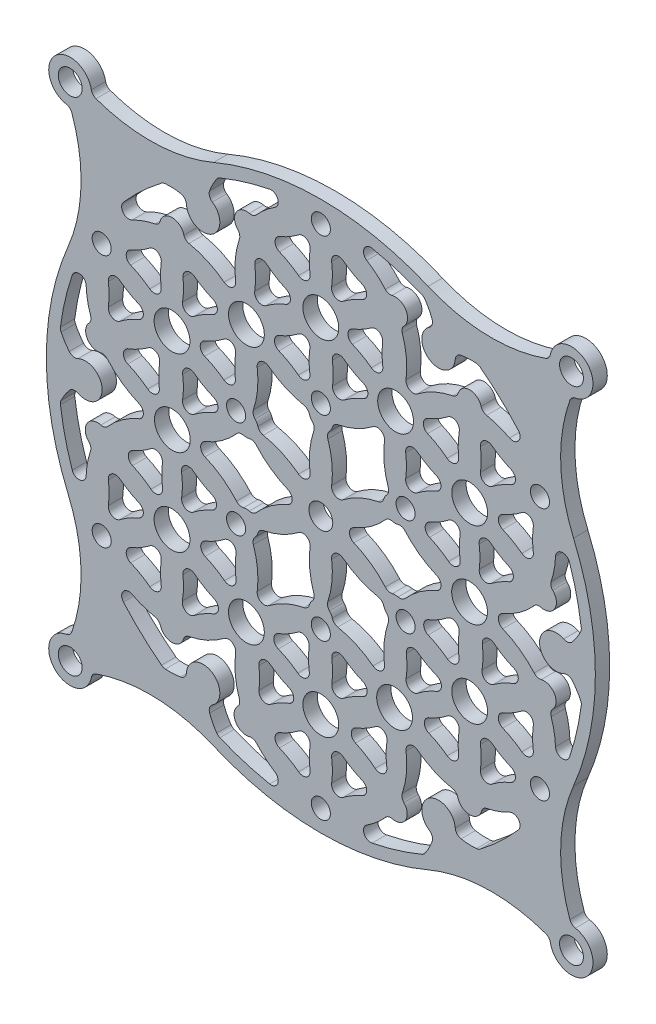
SolidWorks part; units mm, degrees
material "PC Alta Viscosidade"
ref_plane "Plano frontal" through (0, 0, 0) normal (0, 0, 1) x (1, 0, 0)
ref_plane "Plano superior" through (0, 0, 0) normal (0, 1, 0) x (1, 0, 0)
ref_plane "Plano direito" through (0, 0, 0) normal (1, 0, 0) x (0, 0, -1)
sketch "Esboço1" plane through (0, 0, 0) normal (0, 0, 1) x (1, 0, 0)
  line L1 (-60, 60) -> (60, 60)
  line L2 (-60, 60) -> (-60, -60)
  line L3 (-60, -60) -> (60, -60)
  line L4 (60, 60) -> (60, -60)
  line L5 (-60, 60) -> (60, -60) construction
  line L6 (-60, -60) -> (60, 60) construction
  point P0 (0, 0)
  dimension "D1" = 120
  dimension "D2" = 120
extrude "Ressalto-extrusão1" add sketch "Esboço1" along normal blind 3
sketch "Esboço2" plane through (0, 0, 3) normal (0, 0, 1) x (1, 0, 0)
  circle A0 centre (-52.5, 52.5) radius 2.5
  circle A1 centre (52.5, 52.5) radius 2.5
  circle A2 centre (52.5, -52.5) radius 2.5
  circle A3 centre (-52.5, -52.5) radius 2.5
  dimension "D5" = 5
  dimension "D1" = 105
  dimension "D2" = 105
  dimension "D3" = 52.5
  dimension "D4" = 52.5
extrude "Corte-extrusão1" cut sketch "Esboço2" against normal through all
sketch "Esboço3" plane through (0, 0, 3) normal (0, 0, 1) x (1, 0, 0)
  line L0 (0, 54) -> (0, 36) construction
  line L1 (0, 36) -> (0, 18) construction
  line L2 (0, 18) -> (0, 0) construction
  line L3 (0, 36) -> (-15.5885, 45) construction
  line L4 (-15.5885, 45) -> (-15.5885, 27) construction
  line L5 (-15.5885, 27) -> (0, 36) construction
  line L6 (0, 36) -> (15.5885, 45) construction
  line L7 (15.5885, 45) -> (15.5885, 27) construction
  line L8 (15.5885, 27) -> (0, 36) construction
  line L9 (0, 54) -> (-15.5885, 45) construction
  line L10 (0, 54) -> (15.5885, 45) construction
  line L11 (-15.5885, 27) -> (0, 18) construction
  line L12 (0, 18) -> (15.5885, 27) construction
  line L13 (46.7654, 27) -> (31.1769, 18) construction
  line L14 (31.1769, 18) -> (15.5885, 9) construction
  line L15 (15.5885, 9) -> (0, 0) construction
  line L16 (31.1769, 18) -> (31.1769, 36) construction
  line L17 (31.1769, 36) -> (15.5885, 27) construction
  line L18 (15.5885, 27) -> (31.1769, 18) construction
  line L19 (31.1769, 18) -> (46.7654, 9) construction
  line L20 (46.7654, 9) -> (31.1769, 0) construction
  line L21 (31.1769, 0) -> (31.1769, 18) construction
  line L22 (46.7654, 27) -> (31.1769, 36) construction
  line L23 (46.7654, 27) -> (46.7654, 9) construction
  line L24 (15.5885, 27) -> (15.5885, 9) construction
  line L25 (15.5885, 9) -> (31.1769, 0) construction
  line L26 (46.7654, -27) -> (31.1769, -18) construction
  line L27 (31.1769, -18) -> (15.5885, -9) construction
  line L28 (15.5885, -9) -> (0, 0) construction
  line L29 (31.1769, -18) -> (46.7654, -9) construction
  line L30 (46.7654, -9) -> (31.1769, 0) construction
  line L31 (31.1769, 0) -> (31.1769, -18) construction
  line L32 (31.1769, -18) -> (31.1769, -36) construction
  line L33 (31.1769, -36) -> (15.5885, -27) construction
  line L34 (15.5885, -27) -> (31.1769, -18) construction
  line L35 (46.7654, -27) -> (46.7654, -9) construction
  line L36 (46.7654, -27) -> (31.1769, -36) construction
  line L37 (31.1769, 0) -> (15.5885, -9) construction
  line L38 (15.5885, -9) -> (15.5885, -27) construction
  line L39 (0, -54) -> (0, -36) construction
  line L40 (0, -36) -> (0, -18) construction
  line L41 (0, -18) -> (0, 0) construction
  line L42 (0, -36) -> (15.5885, -45) construction
  line L43 (15.5885, -45) -> (15.5885, -27) construction
  line L44 (15.5885, -27) -> (0, -36) construction
  line L45 (0, -36) -> (-15.5885, -45) construction
  line L46 (-15.5885, -45) -> (-15.5885, -27) construction
  line L47 (-15.5885, -27) -> (0, -36) construction
  line L48 (0, -54) -> (15.5885, -45) construction
  line L49 (0, -54) -> (-15.5885, -45) construction
  line L50 (15.5885, -27) -> (0, -18) construction
  line L51 (0, -18) -> (-15.5885, -27) construction
  line L52 (-46.7654, -27) -> (-31.1769, -18) construction
  line L53 (-31.1769, -18) -> (-15.5885, -9) construction
  line L54 (-15.5885, -9) -> (0, 0) construction
  line L55 (-31.1769, -18) -> (-31.1769, -36) construction
  line L56 (-31.1769, -36) -> (-15.5885, -27) construction
  line L57 (-15.5885, -27) -> (-31.1769, -18) construction
  line L58 (-31.1769, -18) -> (-46.7654, -9) construction
  line L59 (-46.7654, -9) -> (-31.1769, 0) construction
  line L60 (-31.1769, 0) -> (-31.1769, -18) construction
  line L61 (-46.7654, -27) -> (-31.1769, -36) construction
  line L62 (-46.7654, -27) -> (-46.7654, -9) construction
  line L63 (-15.5885, -27) -> (-15.5885, -9) construction
  line L64 (-15.5885, -9) -> (-31.1769, 0) construction
  line L65 (-46.7654, 27) -> (-31.1769, 18) construction
  line L66 (-31.1769, 18) -> (-15.5885, 9) construction
  line L67 (-15.5885, 9) -> (0, 0) construction
  line L68 (-31.1769, 18) -> (-46.7654, 9) construction
  line L69 (-46.7654, 9) -> (-31.1769, 0) construction
  line L70 (-31.1769, 0) -> (-31.1769, 18) construction
  line L71 (-31.1769, 18) -> (-31.1769, 36) construction
  line L72 (-31.1769, 36) -> (-15.5885, 27) construction
  line L73 (-15.5885, 27) -> (-31.1769, 18) construction
  line L74 (-46.7654, 27) -> (-46.7654, 9) construction
  line L75 (-46.7654, 27) -> (-31.1769, 36) construction
  line L76 (-31.1769, 0) -> (-15.5885, 9) construction
  line L77 (-15.5885, 9) -> (-15.5885, 27) construction
  line L78 (-46.7654, 27) -> (-49.4666, 28.5596) construction
  line L79 (-46.7654, -27) -> (-49.4666, -28.5596) construction
  line L80 (0, -54) -> (0, -57.1191) construction
  line L81 (46.7654, -27) -> (49.4666, -28.5596) construction
  line L82 (46.7668, 27.0008) -> (49.468, 28.5603) construction
  line L83 (0, 54.0016) -> (0, 57.1207) construction
  line L84 (0, 0) -> (-58.8243, 0) construction
  line L85 (0, 0) -> (-29.4122, 50.9433) construction
  line L86 (-55, 15.414) -> (-55, -15.414) construction
  line L87 (0, 0) -> (29.4122, 50.9433) construction
  line L88 (0, 0) -> (58.8243, 0) construction
  line L89 (0, 0) -> (29.4122, -50.9433) construction
  line L90 (0, 0) -> (-29.4122, -50.9433) construction
  line L92 (-60, 60) -> (60, 60)
  line L93 (-60, 60) -> (-60, -60)
  line L94 (-60, -60) -> (60, -60)
  line L95 (60, 60) -> (60, -60)
  line L96 (-60, 60) -> (60, -60) construction
  line L97 (-60, -60) -> (60, 60) construction
  circle A0 centre (0, 0) radius 2.5
  arc A1 (1.8053, 16.2706) -> (2.4004, 17.3012) centre (0, 18) ccw
  arc A2 (10.7289, -53.9434) -> (21.1741, -50.7608) centre (0, 0) ccw
  circle A3 centre (0, 36) radius 3.75
  arc A4 (21.1578, 50.7676) -> (10.7289, 53.9434) centre (0, 0) ccw
  arc A5 (54.5449, 7.0607) -> (52.0808, 17.6802) centre (0, 0) ccw
  arc A6 (17.3923, 43.1557) -> (14.8932, 47.4843) centre (15.5885, 45) ccw
  circle A7 centre (0, 0) radius 2.5
  arc A8 (-4.6607, 48.6968) -> (-8.6717, 46.3809) centre (-15.6058, 63.0227) cw
  arc A9 (-2.2624, 6.6879) -> (-1.4672, 14.7535) centre (15.5885, 9) cw
  arc A10 (-13.8225, 38.7043) -> (-13.8512, 33.8596) centre (-31.7017, 36.3878) cw
  arc A11 (2.2624, 6.6879) -> (1.4672, 14.7535) centre (-15.5885, 9) ccw
  arc A12 (-8.7861, 25.5898) -> (-4.6996, 23.2379) centre (-15.6761, 8.8919) cw
  arc A13 (3.5451, 18.3526) -> (10.9278, 21.6967) centre (0, 36) ccw
  arc A14 (2.2624, 47.3121) -> (2.2624, 42.6879) centre (-15.5885, 45) cw
  arc A15 (4.8474, 23.4794) -> (8.9109, 25.762) centre (15.6519, 9.0035) cw
  arc A16 (12.981, 33.5962) -> (12.9504, 38.0499) centre (30.8558, 35.9461) cw
  arc A17 (-2.2624, 47.3121) -> (-2.2624, 42.6879) centre (15.5885, 45) ccw
  arc A18 (-7.2635, 37.5306) -> (-11.3861, 40.0588) centre (0, 54) cw
  arc A19 (4.6607, 48.6968) -> (8.6717, 46.3809) centre (15.6058, 63.0227) ccw
  arc A20 (-8.6699, 43.6109) -> (-4.6593, 41.3022) centre (-15.5703, 26.9861) cw
  arc A21 (-4.6996, 30.7041) -> (-8.7834, 28.364) centre (-15.6282, 45.0428) cw
  arc A22 (-11.4689, 32.4471) -> (-7.3171, 34.7633) centre (-0.6864, 17.9983) cw
  arc A23 (-2.303, 29.3166) -> (-2.3009, 24.625) centre (15.5734, 26.9786) ccw
  arc A24 (2.4151, 29.487) -> (2.4608, 24.8594) centre (-15.4407, 26.9968) cw
  arc A25 (4.8111, 30.8864) -> (8.9148, 28.5437) centre (15.5885, 45) ccw
  arc A26 (6.6022, 34.4802) -> (10.5881, 32.205) centre (-0.1345, 18.0496) cw
  arc A27 (4.6593, 41.3022) -> (8.6699, 43.6109) centre (15.5703, 26.9861) cw
  arc A28 (6.6196, 37.263) -> (10.579, 39.4385) centre (0, 54.0016) ccw
  arc A29 (14.9934, 6.5718) -> (16.1835, 6.5718) centre (15.5885, 9) ccw
  arc A30 (-41.3519, -36.2632) -> (-33.3731, -43.7177) centre (0, 0) ccw
  arc A31 (-2.4004, 17.3012) -> (-1.8053, 16.2706) centre (0, 18) ccw
  circle A32 centre (31.1769, 18) radius 3.75
  arc A33 (-21.1578, -50.7676) -> (-10.7289, -53.9434) centre (0, 0) ccw
  arc A34 (-10.9278, 21.6967) -> (-3.5451, 18.3526) centre (0, 36) ccw
  arc A35 (-17.0557, 41.7535) -> (-17.8509, 33.6879) centre (0, 36) ccw
  arc A36 (-14.9934, 47.4282) -> (-17.3938, 43.2706) centre (-15.5885, 45) ccw
  arc A37 (33.3872, -43.707) -> (41.3519, -36.2632) centre (0, 0) ccw
  arc A38 (-9.6335, 51.2051) -> (-13.5106, 47.8939) centre (0, 36) ccw
  arc A39 (-54.5449, -7.0607) -> (-52.0808, -17.6802) centre (0, 0) ccw
  arc A40 (9.6335, 51.2051) -> (10.7289, 53.9434) centre (10.4363, 52.4722) cw
  arc A41 (13.5106, 47.8939) -> (9.6335, 51.2051) centre (0, 36) ccw
  arc A42 (46.0701, 6.5157) -> (48.5692, 10.8443) centre (46.7654, 9) ccw
  arc A43 (39.8423, 28.3846) -> (35.8312, 30.7004) centre (46.7764, 45.0264) cw
  arc A44 (17.8509, 33.6879) -> (17.0557, 41.7535) centre (0, 36) ccw
  arc A45 (-33.3872, 43.707) -> (-41.3519, 36.2632) centre (0, 0) ccw
  arc A46 (4.6607, 5.3033) -> (12.0433, 8.6474) centre (15.5885, -9) cw
  arc A47 (26.6077, 31.3228) -> (22.3976, 28.9253) centre (15.6619, 45.6484) cw
  arc A48 (6.9231, 1.3846) -> (13.5106, 6.1061) centre (0, 18) ccw
  arc A49 (17.7683, 20.4038) -> (17.7748, 15.6889) centre (-0.1375, 18.0219) cw
  arc A50 (17.6664, 6.1061) -> (24.2538, 1.3846) centre (31.1769, 18) ccw
  arc A51 (42.1047, 21.6967) -> (38.1, 19.3846) centre (31.1769, 36) cw
  arc A52 (52.9268, -22.4722) -> (52.9268, 22.4722) centre (0, 0) ccw
  circle A53 centre (-15.5885, 27) radius 3.75
  arc A54 (1.8053, 16.2706) -> (1.4672, 14.7535) centre (2.8885, 15.233) ccw
  arc A55 (-1.8053, 16.2706) -> (-1.4672, 14.7535) centre (-2.8885, 15.233) cw
  arc A56 (-3.5451, 18.3526) -> (-2.4004, 17.3012) centre (-3.8406, 16.8819) cw
  arc A57 (3.5451, 18.3526) -> (2.4004, 17.3012) centre (3.8406, 16.8819) ccw
  arc A58 (-54.4071, 6.1923) -> (-54.5472, 7.0431) centre (-53.0595, 6.851) cw
  arc A59 (-54.4121, -6.2242) -> (-54.5449, -7.0607) centre (-53.0573, -6.8681) ccw
  arc A60 (17.0557, 41.7535) -> (17.3923, 43.1557) centre (18.34, 42.1868) cw
  arc A61 (13.5106, 47.8939) -> (14.8932, 47.4843) centre (14.5279, 48.7895) ccw
  arc A62 (39.5282, 33.9454) -> (41.3519, 36.2632) centre (40.2241, 35.2742) ccw
  arc A63 (-17.0557, 41.7535) -> (-17.3938, 43.2706) centre (-18.477, 42.233) ccw
  arc A64 (-13.5106, 47.8939) -> (-14.9934, 47.4282) centre (-14.6364, 48.8851) cw
  arc A65 (8.9148, 28.5437) -> (8.9109, 25.762) centre (8.3511, 27.1537) cw
  arc A66 (12.981, 33.5962) -> (10.5881, 32.205) centre (11.4938, 33.4006) cw
  arc A67 (12.9504, 38.0499) -> (10.579, 39.4385) centre (11.4606, 38.2249) ccw
  arc A68 (8.6699, 43.6109) -> (8.6717, 46.3809) centre (8.0948, 44.9963) ccw
  arc A69 (2.2624, 47.3121) -> (4.6607, 48.6968) centre (3.75, 47.5048) cw
  arc A70 (2.2624, 42.6879) -> (4.6593, 41.3022) centre (3.75, 42.4952) ccw
  arc A71 (6.6196, 37.263) -> (6.6022, 34.4802) centre (7.1712, 35.8681) ccw
  arc A72 (2.4151, 29.487) -> (4.8111, 30.8864) centre (3.9007, 29.6942) cw
  arc A73 (4.8474, 23.4794) -> (2.4608, 24.8594) centre (3.9502, 24.6815) cw
  arc A74 (-4.6996, 23.2379) -> (-2.3009, 24.625) centre (-3.7881, 24.4292) ccw
  arc A75 (-7.3171, 34.7633) -> (-7.2635, 37.5306) centre (-7.8688, 36.1581) ccw
  arc A76 (-2.303, 29.3166) -> (-4.6996, 30.7041) centre (-3.7903, 29.5111) ccw
  arc A77 (-8.7861, 25.5898) -> (-8.7834, 28.364) centre (-8.2139, 26.9763) cw
  arc A78 (-11.4689, 32.4471) -> (-13.8512, 33.8596) centre (-12.3661, 33.6492) cw
  arc A79 (-13.8225, 38.7043) -> (-11.3861, 40.0588) centre (-12.335, 38.8971) cw
  arc A80 (-2.2624, 47.3121) -> (-4.6607, 48.6968) centre (-3.75, 47.5048) ccw
  arc A81 (-8.6699, 43.6109) -> (-8.6717, 46.3809) centre (-8.0948, 44.9963) cw
  arc A82 (-2.2624, 42.6879) -> (-4.6593, 41.3022) centre (-3.75, 42.4952) cw
  arc A83 (22.7575, 7.5418) -> (26.766, 5.164) centre (15.6232, -9.0532) cw
  arc A84 (35.5856, 5.5562) -> (39.4273, 7.8096) centre (46.5582, -8.7489) cw
  arc A85 (39.8423, 25.6154) -> (35.8376, 23.3033) centre (46.7654, 9) ccw
  arc A86 (28.8707, 25.0557) -> (28.9989, 29.8901) centre (46.7654, 27) cw
  arc A87 (44.5029, 20.3121) -> (44.5029, 15.6805) centre (62.3822, 17.9963) ccw
  arc A88 (33.4332, 29.3138) -> (33.4391, 24.6861) centre (15.5855, 26.9773) cw
  arc A89 (24.2407, 19.422) -> (20.1723, 21.7887) centre (31.1941, 36.0558) cw
  arc A90 (22.3655, 26.1559) -> (26.4473, 23.7184) centre (15.2438, 9.5936) cw
  arc A91 (24.2374, 16.6528) -> (20.1754, 14.3052) centre (31.1509, 0.0024) ccw
  arc A92 (26.7441, 12.652) -> (22.7592, 10.2986) centre (15.6595, 26.8704) cw
  arc A93 (29.1539, 11.2767) -> (29.177, 6.5514) centre (46.7654, 9) ccw
  arc A94 (33.1618, 11.5225) -> (33.1844, 6.9329) centre (15.5642, 9.1413) cw
  arc A95 (38.0984, 16.6161) -> (42.1031, 14.2971) centre (31.1558, 0.0088) cw
  arc A96 (35.5805, 12.8988) -> (39.4443, 10.5575) centre (46.7668, 27.0008) ccw
  arc A97 (13.7831, 10.7294) -> (13.1881, 9.6988) centre (15.5885, 9) ccw
  arc A98 (-32.5662, -44.0218) -> (-33.3731, -43.7177) centre (-32.4629, -42.5254) cw
  arc A99 (13.326, 20.3121) -> (14.1212, 12.2465) centre (31.1769, 18) ccw
  arc A100 (27.6318, 35.6474) -> (20.2491, 32.3033) centre (31.1769, 18) ccw
  arc A101 (33.5773, 36.6988) -> (28.7766, 36.6988) centre (31.1769, 36) ccw
  arc A102 (39.5282, 33.9454) -> (34.7221, 35.6474) centre (31.1769, 18) ccw
  arc A103 (-52.0808, 17.6802) -> (-54.5472, 7.0431) centre (0, 0) ccw
  arc A104 (48.2326, 12.2465) -> (49.1617, 17.2597) centre (31.1769, 18) ccw
  arc A105 (38.1, 1.3846) -> (44.6875, 6.1061) centre (31.1769, 18) ccw
  arc A106 (-21.8157, -50.2343) -> (-21.1578, -50.7676) centre (-20.5807, -49.383) ccw
  circle A107 centre (-31.1002, 0.1263) radius 3.75
  circle A108 centre (-15.5885, -27) radius 3.75
  arc A109 (14.9934, 6.5718) -> (13.5106, 6.1061) centre (14.6364, 5.1149) ccw
  arc A110 (13.1881, 9.6988) -> (12.0433, 8.6474) centre (11.7479, 10.1181) cw
  arc A111 (14.1212, 12.2465) -> (13.7831, 10.7294) centre (12.6999, 11.767) cw
  arc A112 (17.6664, 6.1061) -> (16.1835, 6.5718) centre (16.5405, 5.1149) ccw
  arc A113 (28.3363, 0) -> (28.7766, -0.6988) centre (27.3363, -1.1181) cw
  arc A114 (21.8409, -50.2141) -> (21.1741, -50.7608) centre (20.5966, -49.3764) cw
  arc A115 (44.6875, 6.1061) -> (46.0701, 6.5157) centre (45.7048, 5.2105) cw
  arc A116 (48.2326, 12.2465) -> (48.5692, 10.8443) centre (49.5169, 11.8132) ccw
  arc A117 (-52.0808, 17.6802) -> (-49.1617, 17.2597) centre (-50.6604, 17.198) cw
  arc A118 (27.6318, 35.6474) -> (28.7766, 36.6988) centre (27.3363, 37.1181) ccw
  arc A119 (34.7221, 35.6474) -> (33.5773, 36.6988) centre (35.0175, 37.1181) cw
  arc A120 (29.177, 6.5514) -> (26.766, 5.164) centre (27.6913, 6.3446) cw
  arc A121 (35.5856, 5.5562) -> (33.1844, 6.9329) centre (34.6727, 6.7464) cw
  arc A122 (39.4273, 7.8096) -> (39.4443, 10.5575) centre (38.8341, 9.1873) ccw
  arc A123 (42.1031, 14.2971) -> (44.5029, 15.6805) centre (43.0154, 15.4878) ccw
  arc A124 (42.1047, 21.6967) -> (44.5029, 20.3121) centre (43.0154, 20.5048) cw
  arc A125 (38.1, 19.3846) -> (38.0984, 16.6161) centre (38.6769, 18) ccw
  arc A126 (35.5805, 12.8988) -> (33.1618, 11.5225) centre (34.6483, 11.7236) ccw
  arc A127 (26.7441, 12.652) -> (29.1539, 11.2767) centre (27.6663, 11.469) cw
  arc A128 (22.7575, 7.5418) -> (22.7592, 10.2986) centre (23.3499, 8.9198) cw
  arc A129 (17.7748, 15.6889) -> (20.1754, 14.3052) centre (19.2622, 15.4952) ccw
  arc A130 (26.4473, 23.7184) -> (28.8707, 25.0557) centre (27.3795, 24.8936) ccw
  arc A131 (24.2374, 16.6528) -> (24.2407, 19.422) centre (23.6622, 18.0381) ccw
  arc A132 (17.7683, 20.4038) -> (20.1723, 21.7887) centre (19.2552, 20.6016) cw
  arc A133 (22.3655, 26.1559) -> (22.3976, 28.9253) centre (22.9581, 27.5339) cw
  arc A134 (26.6077, 31.3228) -> (28.9989, 29.8901) centre (27.5184, 30.1309) cw
  arc A135 (39.8423, 25.6154) -> (39.8423, 28.3846) centre (39.2654, 27) ccw
  arc A136 (33.4332, 29.3138) -> (35.8312, 30.7004) centre (34.9206, 29.5085) cw
  arc A137 (35.8376, 23.3033) -> (33.4391, 24.6861) centre (34.9269, 24.4952) cw
  circle A138 centre (0, 0) radius 2.5
  arc A139 (13.1881, -9.6988) -> (13.7831, -10.7294) centre (15.5885, -9) ccw
  arc A140 (-52.0808, -17.6802) -> (-49.1617, -17.2597) centre (-50.6604, -17.198) ccw
  circle A141 centre (31.1769, -18) radius 3.75
  arc A142 (32.5964, -44.0102) -> (33.3872, -43.707) centre (32.4766, -42.5149) ccw
  arc A143 (-39.5282, -33.9454) -> (-41.3519, -36.2632) centre (-40.2241, -35.2742) ccw
  arc A144 (28.6778, -36.64) -> (33.676, -36.64) centre (31.1769, -36) ccw
  arc A145 (44.5029, -20.3121) -> (44.5029, -15.6805) centre (62.3822, -17.9963) cw
  arc A146 (6.9231, -1.3846) -> (13.5106, -6.1061) centre (0, -18) cw
  arc A147 (40.4302, -7.3815) -> (36.2489, -4.9343) centre (47.3636, 9.2606) cw
  arc A148 (4.6607, -5.3033) -> (12.0433, -8.6474) centre (15.5885, 9) ccw
  arc A149 (26.5544, -5.1859) -> (22.4744, -7.549) centre (15.5386, 9.13) cw
  arc A150 (14.1212, -12.2465) -> (13.326, -20.3121) centre (31.1769, -18) ccw
  arc A151 (39.8423, -25.6154) -> (35.8376, -23.3033) centre (46.7654, -9) cw
  arc A152 (17.9101, -15.9377) -> (17.8552, -20.5981) centre (-0.0287, -18.0567) cw
  arc A153 (22.6046, -28.04) -> (26.477, -30.2403) centre (15.7023, -44.695) cw
  arc A154 (42.1047, -21.6967) -> (38.1, -19.3846) centre (31.1769, -36) ccw
  arc A155 (36.1342, -12.4749) -> (40.385, -10.1687) centre (46.7654, -27) cw
  arc A156 (39.8423, -28.3846) -> (35.8312, -30.7004) centre (46.7764, -45.0264) ccw
  arc A157 (42.1031, -14.2971) -> (38.0984, -16.6161) centre (31.1558, -0.0088) cw
  arc A158 (28.9403, -11.2821) -> (28.9557, -6.5754) centre (46.8223, -8.987) cw
  arc A159 (33.8345, -6.2911) -> (33.7644, -11.0448) centre (15.9302, -8.4047) cw
  arc A160 (26.5404, -12.6639) -> (22.4763, -10.3198) centre (15.5775, -26.9763) ccw
  arc A161 (24.329, -16.835) -> (20.2985, -14.5608) centre (31.1002, -0.1263) cw
  arc A162 (24.3428, -19.6097) -> (20.2622, -21.9923) centre (31.1769, -36) ccw
  arc A163 (26.5597, -22.9578) -> (22.5963, -25.272) centre (15.6987, -8.9084) cw
  arc A164 (33.4391, -24.6861) -> (33.4332, -29.3138) centre (15.5855, -26.9773) cw
  arc A165 (28.9609, -24.3642) -> (28.8652, -28.881) centre (46.7668, -27.0008) ccw
  arc A166 (16.1835, -6.5718) -> (14.9934, -6.5718) centre (15.5885, -9) ccw
  arc A167 (-9.6335, -51.2051) -> (-10.7289, -53.9434) centre (-10.4363, -52.4722) cw
  arc A168 (24.2538, -1.3846) -> (17.6664, -6.1061) centre (31.1769, -18) ccw
  arc A169 (44.6875, -6.1061) -> (38.1, -1.3846) centre (31.1769, -18) ccw
  arc A170 (48.5707, -10.7294) -> (46.1704, -6.5718) centre (46.7654, -9) ccw
  arc A171 (49.1617, -17.2597) -> (48.2326, -12.2465) centre (31.1769, -18) ccw
  arc A173 (34.7221, -35.6474) -> (39.5282, -33.9454) centre (31.1769, -18) ccw
  arc A174 (20.2491, -32.3033) -> (27.6318, -35.6474) centre (31.1769, -18) ccw
  circle A176 centre (15.4407, -26.9968) radius 3.75
  circle A177 centre (31.1509, 0.0024) radius 3.75
  arc A178 (13.1881, -9.6988) -> (12.0433, -8.6474) centre (11.7479, -10.1181) ccw
  arc A179 (14.9934, -6.5718) -> (13.5106, -6.1061) centre (14.6364, -5.1149) cw
  arc A180 (17.6664, -6.1061) -> (16.1835, -6.5718) centre (16.5405, -5.1149) cw
  arc A181 (14.1212, -12.2465) -> (13.7831, -10.7294) centre (12.6999, -11.767) ccw
  arc A184 (27.6318, -35.6474) -> (28.6778, -36.64) centre (27.3648, -36.9763) cw
  arc A185 (34.7221, -35.6474) -> (33.676, -36.64) centre (34.989, -36.9763) ccw
  arc A187 (44.6875, -6.1061) -> (46.1704, -6.5718) centre (45.8134, -5.1149) ccw
  arc A188 (48.2326, -12.2465) -> (48.5707, -10.7294) centre (49.6539, -11.767) cw
  arc A189 (20.2622, -21.9923) -> (17.8552, -20.5981) centre (19.3402, -20.8091) cw
  arc A190 (22.6046, -28.04) -> (22.5963, -25.272) centre (23.1789, -26.6543) cw
  arc A191 (26.477, -30.2403) -> (28.8652, -28.881) centre (27.3734, -29.0376) ccw
  arc A192 (33.4332, -29.3138) -> (35.8312, -30.7004) centre (34.9206, -29.5085) ccw
  arc A193 (39.8423, -25.6154) -> (39.8423, -28.3846) centre (39.2654, -27) cw
  arc A194 (35.8376, -23.3033) -> (33.4391, -24.6861) centre (34.9269, -24.4952) ccw
  arc A195 (28.9609, -24.3642) -> (26.5597, -22.9578) centre (27.4771, -24.1445) ccw
  arc A196 (24.329, -16.835) -> (24.3428, -19.6097) centre (23.7656, -18.2252) cw
  arc A197 (17.9101, -15.9377) -> (20.2985, -14.5608) centre (19.3997, -15.7617) cw
  arc A198 (22.4744, -7.549) -> (22.4763, -10.3198) centre (23.0503, -8.934) ccw
  arc A199 (33.7644, -11.0448) -> (36.1342, -12.4749) centre (35.2483, -11.2645) ccw
  arc A200 (26.5404, -12.6639) -> (28.9403, -11.2821) centre (27.4525, -11.473) ccw
  arc A201 (26.5544, -5.1859) -> (28.9557, -6.5754) centre (27.4692, -6.3747) cw
  arc A202 (33.8345, -6.2911) -> (36.2489, -4.9343) centre (35.3241, -6.1153) cw
  arc A203 (40.4302, -7.3815) -> (40.385, -10.1687) centre (39.8533, -8.7661) cw
  arc A204 (42.1047, -21.6967) -> (44.5029, -20.3121) centre (43.0154, -20.5048) ccw
  arc A205 (42.1031, -14.2971) -> (44.5029, -15.6805) centre (43.0154, -15.4878) cw
  arc A206 (38.1, -19.3846) -> (38.0984, -16.6161) centre (38.6769, -18) cw
  circle A207 centre (0, 0) radius 2.5
  arc A208 (-1.8053, -16.2706) -> (-2.4004, -17.3012) centre (0, -18) ccw
  circle A210 centre (0, -36) radius 3.75
  arc A211 (54.5472, -7.0431) -> (54.4071, -6.1923) centre (53.0595, -6.851) ccw
  arc A213 (-17.3923, -43.1557) -> (-14.8932, -47.4843) centre (-15.5885, -45) ccw
  arc A214 (4.6607, -48.6968) -> (8.6717, -46.3809) centre (15.6058, -63.0227) cw
  arc A215 (2.2624, -6.6879) -> (1.4672, -14.7535) centre (-15.5885, -9) cw
  arc A216 (13.8225, -38.7043) -> (13.8512, -33.8596) centre (31.7017, -36.3878) cw
  arc A217 (-2.2624, -6.6879) -> (-1.4672, -14.7535) centre (15.5885, -9) ccw
  arc A218 (8.7861, -25.5898) -> (4.6996, -23.2379) centre (15.6761, -8.8919) cw
  arc A219 (-3.5451, -18.3526) -> (-10.9278, -21.6967) centre (0, -36) ccw
  arc A220 (-2.2624, -47.3121) -> (-2.2624, -42.6879) centre (15.5885, -45) cw
  arc A221 (-4.8474, -23.4794) -> (-8.9109, -25.762) centre (-15.6519, -9.0035) cw
  arc A222 (-12.981, -33.5962) -> (-12.9504, -38.0499) centre (-30.8558, -35.9461) cw
  arc A223 (2.2624, -47.3121) -> (2.2624, -42.6879) centre (-15.5885, -45) ccw
  arc A224 (7.2635, -37.5306) -> (11.3861, -40.0588) centre (0, -54) cw
  arc A225 (-4.6607, -48.6968) -> (-8.6717, -46.3809) centre (-15.6058, -63.0227) ccw
  arc A226 (8.6699, -43.6109) -> (4.6593, -41.3022) centre (15.5703, -26.9861) cw
  arc A227 (4.6996, -30.7041) -> (8.7834, -28.364) centre (15.6282, -45.0428) cw
  arc A228 (11.4689, -32.4471) -> (7.3171, -34.7633) centre (0.6864, -17.9983) cw
  arc A229 (2.303, -29.3166) -> (2.3009, -24.625) centre (-15.5734, -26.9786) ccw
  arc A230 (-2.4151, -29.487) -> (-2.4608, -24.8594) centre (15.4407, -26.9968) cw
  arc A231 (-4.8111, -30.8864) -> (-8.9148, -28.5437) centre (-15.5885, -45) ccw
  arc A232 (-6.6022, -34.4802) -> (-10.5881, -32.205) centre (0.1345, -18.0496) cw
  arc A233 (-4.6593, -41.3022) -> (-8.6699, -43.6109) centre (-15.5703, -26.9861) cw
  arc A234 (-6.6196, -37.263) -> (-10.579, -39.4385) centre (0, -54.0016) ccw
  arc A235 (2.4004, -17.3012) -> (1.8053, -16.2706) centre (0, -18) ccw
  arc A236 (54.4121, 6.2242) -> (54.5449, 7.0607) centre (53.0573, 6.8681) ccw
  arc A237 (10.9278, -21.6967) -> (3.5451, -18.3526) centre (0, -36) ccw
  arc A238 (17.0557, -41.7535) -> (17.8509, -33.6879) centre (0, -36) ccw
  arc A239 (14.9934, -47.4282) -> (17.3938, -43.2706) centre (15.5885, -45) ccw
  arc A240 (9.6335, -51.2051) -> (13.5106, -47.8939) centre (0, -36) ccw
  arc A242 (-13.5106, -47.8939) -> (-9.6335, -51.2051) centre (0, -36) ccw
  arc A243 (-17.8509, -33.6879) -> (-17.0557, -41.7535) centre (0, -36) ccw
  arc A244 (33.3731, 43.7177) -> (32.5662, 44.0218) centre (32.4629, 42.5254) ccw
  circle A245 centre (15.6595, 26.8704) radius 3.75
  arc A246 (21.8157, 50.2343) -> (21.1578, 50.7676) centre (20.5807, 49.383) ccw
  arc A247 (-1.8053, -16.2706) -> (-1.4672, -14.7535) centre (-2.8885, -15.233) ccw
  arc A248 (1.8053, -16.2706) -> (1.4672, -14.7535) centre (2.8885, -15.233) cw
  arc A249 (3.5451, -18.3526) -> (2.4004, -17.3012) centre (3.8406, -16.8819) cw
  arc A250 (-3.5451, -18.3526) -> (-2.4004, -17.3012) centre (-3.8406, -16.8819) ccw
  arc A251 (-21.8409, 50.2141) -> (-21.1741, 50.7608) centre (-20.5966, 49.3764) cw
  arc A252 (-32.5964, 44.0102) -> (-33.3872, 43.707) centre (-32.4766, 42.5149) ccw
  arc A253 (-17.0557, -41.7535) -> (-17.3923, -43.1557) centre (-18.34, -42.1868) cw
  arc A254 (-13.5106, -47.8939) -> (-14.8932, -47.4843) centre (-14.5279, -48.7895) ccw
  arc A256 (17.0557, -41.7535) -> (17.3938, -43.2706) centre (18.477, -42.233) ccw
  arc A257 (13.5106, -47.8939) -> (14.9934, -47.4282) centre (14.6364, -48.8851) cw
  arc A258 (-8.9148, -28.5437) -> (-8.9109, -25.762) centre (-8.3511, -27.1537) cw
  arc A259 (-12.981, -33.5962) -> (-10.5881, -32.205) centre (-11.4938, -33.4006) cw
  arc A260 (-12.9504, -38.0499) -> (-10.579, -39.4385) centre (-11.4606, -38.2249) ccw
  arc A261 (-8.6699, -43.6109) -> (-8.6717, -46.3809) centre (-8.0948, -44.9963) ccw
  arc A262 (-2.2624, -47.3121) -> (-4.6607, -48.6968) centre (-3.75, -47.5048) cw
  arc A263 (-2.2624, -42.6879) -> (-4.6593, -41.3022) centre (-3.75, -42.4952) ccw
  arc A264 (-6.6196, -37.263) -> (-6.6022, -34.4802) centre (-7.1712, -35.8681) ccw
  arc A265 (-2.4151, -29.487) -> (-4.8111, -30.8864) centre (-3.9007, -29.6942) cw
  arc A266 (-4.8474, -23.4794) -> (-2.4608, -24.8594) centre (-3.9502, -24.6815) cw
  arc A267 (4.6996, -23.2379) -> (2.3009, -24.625) centre (3.7881, -24.4292) ccw
  arc A268 (7.3171, -34.7633) -> (7.2635, -37.5306) centre (7.8688, -36.1581) ccw
  arc A269 (2.303, -29.3166) -> (4.6996, -30.7041) centre (3.7903, -29.5111) ccw
  arc A270 (8.7861, -25.5898) -> (8.7834, -28.364) centre (8.2139, -26.9763) cw
  arc A271 (11.4689, -32.4471) -> (13.8512, -33.8596) centre (12.3661, -33.6492) cw
  arc A272 (13.8225, -38.7043) -> (11.3861, -40.0588) centre (12.335, -38.8971) cw
  arc A273 (2.2624, -47.3121) -> (4.6607, -48.6968) centre (3.75, -47.5048) ccw
  arc A274 (8.6699, -43.6109) -> (8.6717, -46.3809) centre (8.0948, -44.9963) cw
  arc A275 (2.2624, -42.6879) -> (4.6593, -41.3022) centre (3.75, -42.4952) cw
  arc A276 (-10.7289, 53.9434) -> (-21.1741, 50.7608) centre (0, 0) ccw
  arc A277 (-14.9934, -6.5718) -> (-16.1835, -6.5718) centre (-15.5885, -9) ccw
  circle A279 centre (-31.1769, -18) radius 3.75
  arc A280 (-50.8588, -3.1379) -> (-50.8666, 3.134) centre (-49.3084, 0) ccw
  arc A281 (-52.671, -3.5171) -> (-50.8588, -3.1379) centre (-51.5232, -4.4827) cw
  arc A282 (-46.0701, -6.5157) -> (-48.5692, -10.8443) centre (-46.7654, -9) ccw
  arc A283 (-39.8423, -28.3846) -> (-35.8312, -30.7004) centre (-46.7764, -45.0264) cw
  arc A284 (-4.6607, -5.3033) -> (-12.0433, -8.6474) centre (-15.5885, 9) cw
  arc A285 (-26.6077, -31.3228) -> (-22.3976, -28.9253) centre (-15.6619, -45.6484) cw
  arc A286 (-6.9231, -1.3846) -> (-13.5106, -6.1061) centre (0, -18) ccw
  arc A287 (-17.7683, -20.4038) -> (-17.7748, -15.6889) centre (0.1375, -18.0219) cw
  arc A288 (-17.6664, -6.1061) -> (-24.2538, -1.3846) centre (-31.1769, -18) ccw
  arc A289 (-42.1047, -21.6967) -> (-38.1, -19.3846) centre (-31.1769, -36) cw
  arc A290 (-22.7575, -7.5418) -> (-26.766, -5.164) centre (-15.6232, 9.0532) cw
  arc A291 (-35.5856, -5.5562) -> (-39.4273, -7.8096) centre (-46.5582, 8.7489) cw
  arc A292 (-39.8423, -25.6154) -> (-35.8376, -23.3033) centre (-46.7654, -9) ccw
  arc A293 (-28.8707, -25.0557) -> (-28.9989, -29.8901) centre (-46.7654, -27) cw
  arc A294 (-44.5029, -20.3121) -> (-44.5029, -15.6805) centre (-62.3822, -17.9963) ccw
  arc A295 (-33.4332, -29.3138) -> (-33.4391, -24.6861) centre (-15.5855, -26.9773) cw
  arc A296 (-24.2407, -19.422) -> (-20.1723, -21.7887) centre (-31.1941, -36.0558) cw
  arc A297 (-22.3655, -26.1559) -> (-26.4473, -23.7184) centre (-15.2438, -9.5936) cw
  arc A298 (-24.2374, -16.6528) -> (-20.1754, -14.3052) centre (-31.1509, -0.0024) ccw
  arc A299 (-26.7441, -12.652) -> (-22.7592, -10.2986) centre (-15.6595, -26.8704) cw
  arc A300 (-29.1539, -11.2767) -> (-29.177, -6.5514) centre (-46.7654, -9) ccw
  arc A301 (-33.1618, -11.5225) -> (-33.1844, -6.9329) centre (-15.5642, -9.1413) cw
  arc A302 (-38.0984, -16.6161) -> (-42.1031, -14.2971) centre (-31.1558, -0.0088) cw
  arc A303 (-35.5805, -12.8988) -> (-39.4443, -10.5575) centre (-46.7668, -27.0008) ccw
  arc A304 (-13.7831, -10.7294) -> (-13.1881, -9.6988) centre (-15.5885, -9) ccw
  arc A305 (-52.6938, 3.5253) -> (-50.8666, 3.134) centre (-51.5344, 4.4772) ccw
  arc A306 (-13.326, -20.3121) -> (-14.1212, -12.2465) centre (-31.1769, -18) ccw
  arc A307 (-27.6318, -35.6474) -> (-20.2491, -32.3033) centre (-31.1769, -18) ccw
  arc A308 (-33.5773, -36.6988) -> (-28.7766, -36.6988) centre (-31.1769, -36) ccw
  arc A309 (-39.5282, -33.9454) -> (-34.7221, -35.6474) centre (-31.1769, -18) ccw
  arc A311 (-48.2326, -12.2465) -> (-49.1617, -17.2597) centre (-31.1769, -18) ccw
  arc A312 (-38.1, -1.3846) -> (-44.6875, -6.1061) centre (-31.1769, -18) ccw
  arc A313 (-54.4071, 6.1923) -> (-52.6938, 3.5253) centre (-42.1447, 12.1865) ccw
  arc A314 (-52.671, -3.5171) -> (-54.4121, -6.2242) centre (-43.0137, -11.6416) ccw
  arc A315 (-28.1469, 42.476) -> (-22.7192, 45.6188) centre (-24.6542, 42.7024) ccw
  arc A316 (-14.9934, -6.5718) -> (-13.5106, -6.1061) centre (-14.6364, -5.1149) ccw
  arc A317 (-13.1881, -9.6988) -> (-12.0433, -8.6474) centre (-11.7479, -10.1181) cw
  arc A318 (-14.1212, -12.2465) -> (-13.7831, -10.7294) centre (-12.6999, -11.767) cw
  arc A319 (-17.6664, -6.1061) -> (-16.1835, -6.5718) centre (-16.5405, -5.1149) ccw
  arc A320 (-29.3814, 43.8559) -> (-28.1469, 42.476) centre (-29.6438, 42.379) cw
  arc A321 (-23.2939, 47.3968) -> (-22.7192, 45.6188) centre (-21.8899, 46.8687) ccw
  arc A322 (-44.6875, -6.1061) -> (-46.0701, -6.5157) centre (-45.7048, -5.2105) cw
  arc A323 (-48.2326, -12.2465) -> (-48.5692, -10.8443) centre (-49.5169, -11.8132) ccw
  arc A325 (-27.6318, -35.6474) -> (-28.7766, -36.6988) centre (-27.3363, -37.1181) ccw
  arc A326 (-34.7221, -35.6474) -> (-33.5773, -36.6988) centre (-35.0175, -37.1181) cw
  arc A327 (-29.177, -6.5514) -> (-26.766, -5.164) centre (-27.6913, -6.3446) cw
  arc A328 (-35.5856, -5.5562) -> (-33.1844, -6.9329) centre (-34.6727, -6.7464) cw
  arc A329 (-39.4273, -7.8096) -> (-39.4443, -10.5575) centre (-38.8341, -9.1873) ccw
  arc A330 (-42.1031, -14.2971) -> (-44.5029, -15.6805) centre (-43.0154, -15.4878) ccw
  arc A331 (-42.1047, -21.6967) -> (-44.5029, -20.3121) centre (-43.0154, -20.5048) cw
  arc A332 (-38.1, -19.3846) -> (-38.0984, -16.6161) centre (-38.6769, -18) ccw
  arc A333 (-35.5805, -12.8988) -> (-33.1618, -11.5225) centre (-34.6483, -11.7236) ccw
  arc A334 (-26.7441, -12.652) -> (-29.1539, -11.2767) centre (-27.6663, -11.469) cw
  arc A335 (-22.7575, -7.5418) -> (-22.7592, -10.2986) centre (-23.3499, -8.9198) cw
  arc A336 (-17.7748, -15.6889) -> (-20.1754, -14.3052) centre (-19.2622, -15.4952) ccw
  arc A337 (-26.4473, -23.7184) -> (-28.8707, -25.0557) centre (-27.3795, -24.8936) ccw
  arc A338 (-24.2374, -16.6528) -> (-24.2407, -19.422) centre (-23.6622, -18.0381) ccw
  arc A339 (-17.7683, -20.4038) -> (-20.1723, -21.7887) centre (-19.2552, -20.6016) cw
  arc A340 (-22.3655, -26.1559) -> (-22.3976, -28.9253) centre (-22.9581, -27.5339) cw
  arc A341 (-26.6077, -31.3228) -> (-28.9989, -29.8901) centre (-27.5184, -30.1309) cw
  arc A342 (-39.8423, -25.6154) -> (-39.8423, -28.3846) centre (-39.2654, -27) ccw
  arc A343 (-33.4332, -29.3138) -> (-35.8312, -30.7004) centre (-34.9206, -29.5085) cw
  arc A344 (-35.8376, -23.3033) -> (-33.4391, -24.6861) centre (-34.9269, -24.4952) cw
  arc A346 (-13.1881, 9.6988) -> (-13.7831, 10.7294) centre (-15.5885, 9) ccw
  arc A347 (49.1617, 17.2597) -> (52.0808, 17.6802) centre (50.6604, 17.198) cw
  circle A348 centre (-31.1769, 18) radius 3.75
  arc A349 (-21.8409, 50.2141) -> (-23.2939, 47.3968) centre (-10.5185, 42.5916) ccw
  arc A350 (-29.3814, 43.8559) -> (-32.5964, 44.0102) centre (-31.5888, 31.4302) ccw
  arc A351 (-28.6778, 36.64) -> (-33.676, 36.64) centre (-31.1769, 36) ccw
  arc A352 (-44.5029, 20.3121) -> (-44.5029, 15.6805) centre (-62.3822, 17.9963) cw
  arc A353 (-6.9231, 1.3846) -> (-13.5106, 6.1061) centre (0, 18) cw
  arc A354 (-40.4302, 7.3815) -> (-36.2489, 4.9343) centre (-47.3636, -9.2606) cw
  arc A355 (-4.6607, 5.3033) -> (-12.0433, 8.6474) centre (-15.5885, -9) ccw
  arc A356 (-26.5544, 5.1859) -> (-22.4744, 7.549) centre (-15.5386, -9.13) cw
  arc A357 (-14.1212, 12.2465) -> (-13.326, 20.3121) centre (-31.1769, 18) ccw
  arc A358 (-39.8423, 25.6154) -> (-35.8376, 23.3033) centre (-46.7654, 9) cw
  arc A359 (-17.9101, 15.9377) -> (-17.8552, 20.5981) centre (0.0287, 18.0567) cw
  arc A360 (-22.6046, 28.04) -> (-26.477, 30.2403) centre (-15.7023, 44.695) cw
  arc A361 (-42.1047, 21.6967) -> (-38.1, 19.3846) centre (-31.1769, 36) ccw
  arc A362 (-36.1342, 12.4749) -> (-40.385, 10.1687) centre (-46.7654, 27) cw
  arc A363 (-39.8423, 28.3846) -> (-35.8312, 30.7004) centre (-46.7764, 45.0264) ccw
  arc A364 (-42.1031, 14.2971) -> (-38.0984, 16.6161) centre (-31.1558, 0.0088) cw
  arc A365 (-28.9403, 11.2821) -> (-28.9557, 6.5754) centre (-46.8223, 8.987) cw
  arc A366 (-33.8345, 6.2911) -> (-33.7644, 11.0448) centre (-15.9302, 8.4047) cw
  arc A367 (-26.5404, 12.6639) -> (-22.4763, 10.3198) centre (-15.5775, 26.9763) ccw
  arc A368 (-24.329, 16.835) -> (-20.2985, 14.5608) centre (-31.1002, 0.1263) cw
  arc A369 (-24.3428, 19.6097) -> (-20.2622, 21.9923) centre (-31.1769, 36) ccw
  arc A370 (-26.5597, 22.9578) -> (-22.5963, 25.272) centre (-15.6987, 8.9084) cw
  arc A371 (-33.4391, 24.6861) -> (-33.4332, 29.3138) centre (-15.5855, 26.9773) cw
  arc A372 (-28.9609, 24.3642) -> (-28.8652, 28.881) centre (-46.7668, 27.0008) ccw
  arc A373 (-16.1835, 6.5718) -> (-14.9934, 6.5718) centre (-15.5885, 9) ccw
  arc A374 (22.7119, 45.6139) -> (28.1475, 42.4848) centre (24.6542, 42.7024) ccw
  arc A375 (-24.2538, 1.3846) -> (-17.6664, 6.1061) centre (-31.1769, 18) ccw
  arc A376 (-44.6875, 6.1061) -> (-38.1, 1.3846) centre (-31.1769, 18) ccw
  arc A377 (-48.5707, 10.7294) -> (-46.1704, 6.5718) centre (-46.7654, 9) ccw
  arc A378 (-49.1617, 17.2597) -> (-48.2326, 12.2465) centre (-31.1769, 18) ccw
  arc A379 (49.1617, -17.2597) -> (52.0808, -17.6802) centre (50.6604, -17.198) ccw
  arc A380 (-34.7221, 35.6474) -> (-39.5282, 33.9454) centre (-31.1769, 18) ccw
  arc A381 (-20.2491, 32.3033) -> (-27.6318, 35.6474) centre (-31.1769, 18) ccw
  arc A382 (23.2896, 47.373) -> (22.7119, 45.6139) centre (21.8794, 46.8618) cw
  arc A383 (29.3999, 43.8715) -> (28.1475, 42.4848) centre (29.6446, 42.3916) ccw
  arc A384 (32.5662, 44.0218) -> (29.3999, 43.8715) centre (31.6261, 30.4051) ccw
  arc A385 (-13.1881, 9.6988) -> (-12.0433, 8.6474) centre (-11.7479, 10.1181) ccw
  arc A386 (-14.9934, 6.5718) -> (-13.5106, 6.1061) centre (-14.6364, 5.1149) cw
  arc A387 (-17.6664, 6.1061) -> (-16.1835, 6.5718) centre (-16.5405, 5.1149) cw
  arc A388 (-14.1212, 12.2465) -> (-13.7831, 10.7294) centre (-12.6999, 11.767) ccw
  arc A389 (23.2896, 47.373) -> (21.8157, 50.2343) centre (11.4249, 43.0718) ccw
  arc A390 (50.8588, 3.1379) -> (50.8666, -3.134) centre (49.3084, 0) ccw
  arc A391 (-27.6318, 35.6474) -> (-28.6778, 36.64) centre (-27.3648, 36.9763) cw
  arc A392 (-34.7221, 35.6474) -> (-33.676, 36.64) centre (-34.989, 36.9763) ccw
  arc A394 (-44.6875, 6.1061) -> (-46.1704, 6.5718) centre (-45.8134, 5.1149) ccw
  arc A395 (-48.2326, 12.2465) -> (-48.5707, 10.7294) centre (-49.6539, 11.767) cw
  arc A396 (-20.2622, 21.9923) -> (-17.8552, 20.5981) centre (-19.3402, 20.8091) cw
  arc A397 (-22.6046, 28.04) -> (-22.5963, 25.272) centre (-23.1789, 26.6543) cw
  arc A398 (-26.477, 30.2403) -> (-28.8652, 28.881) centre (-27.3734, 29.0376) ccw
  arc A399 (-33.4332, 29.3138) -> (-35.8312, 30.7004) centre (-34.9206, 29.5085) ccw
  arc A400 (-39.8423, 25.6154) -> (-39.8423, 28.3846) centre (-39.2654, 27) cw
  arc A401 (-35.8376, 23.3033) -> (-33.4391, 24.6861) centre (-34.9269, 24.4952) ccw
  arc A402 (-28.9609, 24.3642) -> (-26.5597, 22.9578) centre (-27.4771, 24.1445) ccw
  arc A403 (-24.329, 16.835) -> (-24.3428, 19.6097) centre (-23.7656, 18.2252) cw
  arc A404 (-17.9101, 15.9377) -> (-20.2985, 14.5608) centre (-19.3997, 15.7617) cw
  arc A405 (-22.4744, 7.549) -> (-22.4763, 10.3198) centre (-23.0503, 8.934) ccw
  arc A406 (-33.7644, 11.0448) -> (-36.1342, 12.4749) centre (-35.2483, 11.2645) ccw
  arc A407 (-26.5404, 12.6639) -> (-28.9403, 11.2821) centre (-27.4525, 11.473) ccw
  arc A408 (-26.5544, 5.1859) -> (-28.9557, 6.5754) centre (-27.4692, 6.3747) cw
  arc A409 (-33.8345, 6.2911) -> (-36.2489, 4.9343) centre (-35.3241, 6.1153) cw
  arc A410 (-40.4302, 7.3815) -> (-40.385, 10.1687) centre (-39.8533, 8.7661) cw
  arc A411 (-42.1047, 21.6967) -> (-44.5029, 20.3121) centre (-43.0154, 20.5048) ccw
  arc A412 (-42.1031, 14.2971) -> (-44.5029, 15.6805) centre (-43.0154, 15.4878) cw
  arc A413 (-38.1, 19.3846) -> (-38.0984, 16.6161) centre (-38.6769, 18) cw
  arc A414 (52.671, 3.5171) -> (50.8588, 3.1379) centre (51.5232, 4.4827) cw
  arc A415 (-4.6607, -5.3033) -> (-2.2624, -6.6879) centre (-3.75, -6.4952) cw
  arc A416 (2.2624, -6.6879) -> (4.6607, -5.3033) centre (3.75, -6.4952) cw
  arc A417 (6.9231, -1.3846) -> (6.9231, 1.3846) centre (7.5, 0) cw
  arc A418 (4.6607, 5.3033) -> (2.2624, 6.6879) centre (3.75, 6.4952) cw
  arc A419 (-2.2624, 6.6879) -> (-4.6607, 5.3033) centre (-3.75, 6.4952) cw
  arc A420 (-6.9231, -1.3846) -> (-6.9231, 1.3846) centre (-7.5, 0) ccw
  arc A421 (13.326, 20.3121) -> (10.9278, 21.6967) centre (11.8385, 20.5048) ccw
  arc A422 (-10.9278, 21.6967) -> (-13.326, 20.3121) centre (-11.8385, 20.5048) ccw
  arc A423 (-24.2538, 1.3846) -> (-24.2538, -1.3846) centre (-23.6769, 0) ccw
  arc A424 (-13.326, -20.3121) -> (-10.9278, -21.6967) centre (-11.8385, -20.5048) ccw
  arc A425 (13.326, -20.3121) -> (10.9278, -21.6967) centre (11.8385, -20.5048) cw
  arc A426 (24.2538, -1.3846) -> (24.2538, 1.3846) centre (23.6769, 0) ccw
  arc A427 (38.1, 1.3846) -> (38.1, -1.3846) centre (38.6769, 0) ccw
  arc A428 (20.2491, -32.3033) -> (17.8509, -33.6879) centre (19.3385, -33.4952) ccw
  arc A429 (-17.8509, -33.6879) -> (-20.2491, -32.3033) centre (-19.3385, -33.4952) ccw
  arc A430 (-38.1, -1.3846) -> (-38.1, 1.3846) centre (-38.6769, 0) ccw
  arc A431 (20.2491, 32.3033) -> (17.8509, 33.6879) centre (19.3385, 33.4952) cw
  arc A432 (-17.8509, 33.6879) -> (-20.2491, 32.3033) centre (-19.3385, 33.4952) cw
  arc A433 (52.6938, -3.5253) -> (50.8666, -3.134) centre (51.5344, -4.4772) ccw
  arc A434 (54.4071, -6.1923) -> (52.6938, -3.5253) centre (42.1447, -12.1865) ccw
  arc A435 (41.3519, 36.2632) -> (33.3731, 43.7177) centre (0, 0) ccw
  arc A436 (52.0808, -17.6802) -> (54.5472, -7.0431) centre (0, 0) ccw
  circle A439 centre (0, 0) radius 55 construction
  arc A440 (-39.5282, 33.9454) -> (-41.3519, 36.2632) centre (-40.2241, 35.2742) cw
  arc A441 (-9.6335, 51.2051) -> (-10.7289, 53.9434) centre (-10.4363, 52.4722) ccw
  arc A442 (39.5282, -33.9454) -> (41.3519, -36.2632) centre (40.2241, -35.2742) cw
  arc A443 (9.6335, -51.2051) -> (10.7289, -53.9434) centre (10.4363, -52.4722) ccw
  arc A464 (52.671, 3.5171) -> (54.4121, 6.2242) centre (43.0137, 11.6416) ccw
  arc A465 (28.1469, -42.476) -> (22.7192, -45.6188) centre (24.6542, -42.7024) ccw
  arc A466 (29.3814, -43.8559) -> (28.1469, -42.476) centre (29.6438, -42.379) cw
  arc A467 (23.2939, -47.3968) -> (22.7192, -45.6188) centre (21.8899, -46.8687) ccw
  arc A468 (21.8409, -50.2141) -> (23.2939, -47.3968) centre (10.5185, -42.5916) ccw
  arc A469 (29.3814, -43.8559) -> (32.5964, -44.0102) centre (31.5888, -31.4302) ccw
  arc A470 (-22.7119, -45.6139) -> (-28.1475, -42.4848) centre (-24.6542, -42.7024) ccw
  arc A471 (-23.2896, -47.373) -> (-22.7119, -45.6139) centre (-21.8794, -46.8618) cw
  arc A472 (-29.3999, -43.8715) -> (-28.1475, -42.4848) centre (-29.6446, -42.3916) ccw
  arc A473 (-32.5662, -44.0218) -> (-29.3999, -43.8715) centre (-31.6261, -30.4051) ccw
  arc A474 (-23.2896, -47.373) -> (-21.8157, -50.2343) centre (-11.4249, -43.0718) ccw
  arc A481 (-48.0736, 53.3107) -> (-53.3107, 48.0736) centre (-52.5, 52.5) ccw
  arc A482 (53.3107, 48.0736) -> (48.0736, 53.3107) centre (52.5, 52.5) ccw
  arc A483 (-53.3107, -48.0736) -> (-48.0736, -53.3107) centre (-52.5, -52.5) ccw
  arc A484 (48.0736, -53.3107) -> (53.3107, -48.0736) centre (52.5, -52.5) ccw
  arc A485 (-52.1668, 47.0981) -> (-52.9268, 22.4722) centre (-84.2296, 35.7631) cw
  arc A486 (-47.0981, 52.1668) -> (-22.4722, 52.9268) centre (-35.7631, 84.2296) ccw
  arc A487 (22.4722, 52.9268) -> (47.0981, 52.1668) centre (35.7631, 84.2296) ccw
  arc A488 (52.1668, 47.0981) -> (52.9268, 22.4722) centre (84.2296, 35.7631) ccw
  arc A489 (47.0981, -52.1668) -> (22.4722, -52.9268) centre (35.7631, -84.2296) ccw
  arc A490 (52.1668, -47.0981) -> (52.9268, -22.4722) centre (84.2296, -35.7631) cw
  arc A491 (-47.0981, -52.1668) -> (-22.4722, -52.9268) centre (-35.7631, -84.2296) cw
  arc A492 (-52.1668, -47.0981) -> (-52.9268, -22.4722) centre (-84.2296, -35.7631) ccw
  arc A493 (22.4722, 52.9268) -> (-22.4722, 52.9268) centre (0, 0) ccw
  arc A494 (-22.4722, -52.9268) -> (22.4722, -52.9268) centre (0, 0) ccw
  arc A495 (-52.9268, 22.4722) -> (-52.9268, -22.4722) centre (0, 0) ccw
  arc A496 (-52.1668, -47.0981) -> (-53.3107, -48.0736) centre (-53.581, -46.5982) cw
  arc A497 (-52.1668, 47.0981) -> (-53.3107, 48.0736) centre (-53.581, 46.5982) ccw
  arc A498 (-47.0981, 52.1668) -> (-48.0736, 53.3107) centre (-46.5982, 53.581) cw
  arc A499 (47.0981, 52.1668) -> (48.0736, 53.3107) centre (46.5982, 53.581) ccw
  arc A500 (52.1668, 47.0981) -> (53.3107, 48.0736) centre (53.581, 46.5982) cw
  arc A501 (52.1668, -47.0981) -> (53.3107, -48.0736) centre (53.581, -46.5982) ccw
  arc A502 (47.0981, -52.1668) -> (48.0736, -53.3107) centre (46.5982, -53.581) cw
  arc A503 (-47.0981, -52.1668) -> (-48.0736, -53.3107) centre (-46.5982, -53.581) ccw
  point P45 (-14.1911, 24.927)
  point P89 (-2.494, 18.1736)
  point P94 (14.1911, 24.927)
  point P97 (16.6851, 29.2466)
  point P108 (-14.1911, 47.073)
  point P402 (-54.5983, -6.6348)
  point P434 (-21.5532, -50.601)
  point P446 (21.5784, -50.5903)
  point P449 (33.0451, -43.9661)
  point P541 (54.5983, 6.6348)
  point P695 (21.5532, 50.601)
  point P784 (0, 0)
  point P842 (-33.0451, 43.9661)
  point P971 (0, 0)
  point P975 (-52.5, -48)
  point P1012 (-52.5, 48)
  point P1015 (-48, 52.5)
  point P1018 (48, 52.5)
  point P1021 (52.5, 48)
  point P1024 (52.5, -48)
  point P1027 (48, -52.5)
  point P1030 (-48, -52.5)
  dimension "D1" = 18
  dimension "D4" = 7.5
  dimension "D3" = 18
  dimension "D6" = 7.5
  dimension "D7" = 18
  dimension "D8" = 1.5
  dimension "D10" = 1.5
  dimension "D11" = 1.5
  dimension "D12" = 1.5
  dimension "D13" = 1.5
  dimension "D15" = 110
  dimension "D20" = 7
  dimension "D21" = 1.5
  dimension "D19" = 9
  dimension "D23" = 115
  dimension "D24" = 34.0075
  dimension "D25" = 1.5
  dimension "D26" = 1.5
  dimension "D17" = 57.1207
  dimension "D18" = 6
  dimension "D22" = 55
  dimension "D27" = 120
  dimension "D9" = 6
extrude "Corte-extrusão2" cut sketch "Esboço3" against normal through all
sketch "Esboço4" plane through (0, 0, 3) normal (0, 0, 1) x (1, 0, 0)
  line L0 (0, 0) -> (-17.7535, 10.25) construction
  line L1 (0, 0) -> (-45.8993, -26.5) construction
  line L2 (-18.7761, 0) -> (0, 0) construction
  line L3 (0, 0) -> (0, 20.5) construction
  line L4 (0, 0) -> (-45.8993, 26.5) construction
  line L5 (-9.3881, 16.2606) -> (0, 0) construction
  line L6 (0, 0) -> (17.7535, 10.25) construction
  line L7 (0, 0) -> (0, 53) construction
  line L8 (9.3881, 16.2606) -> (0, 0) construction
  line L9 (0, 0) -> (17.7535, -10.25) construction
  line L10 (0, 0) -> (45.8993, 26.5) construction
  line L11 (18.7761, 0) -> (0, 0) construction
  line L12 (0, 0) -> (0, -20.5) construction
  line L13 (0, 0) -> (45.8993, -26.5) construction
  line L14 (9.3881, -16.2606) -> (0, 0) construction
  line L15 (0, 0) -> (-17.7535, -10.25) construction
  line L16 (0, 0) -> (0, -53) construction
  line L17 (-9.3881, -16.2606) -> (0, 0) construction
  circle A0 centre (-17.7535, 10.25) radius 2
  circle A1 centre (-45.8993, -26.5) radius 2
  circle A3 centre (0, 20.5) radius 2
  circle A4 centre (-45.8993, 26.5) radius 2
  circle A5 centre (17.7535, 10.25) radius 2
  circle A6 centre (0, 53) radius 2
  circle A7 centre (17.7535, -10.25) radius 2
  circle A8 centre (45.8993, 26.5) radius 2
  circle A9 centre (0, -20.5) radius 2
  circle A10 centre (45.8993, -26.5) radius 2
  circle A11 centre (-17.7535, -10.25) radius 2
  circle A12 centre (0, -53) radius 2
  point P37 (0, 0)
  dimension "D3" = 4
  dimension "D5" = 4
  dimension "D1" = 30
  dimension "D2" = 20.5
  dimension "D4" = 30
  dimension "D6" = 53
extrude "Corte-extrusão3" cut sketch "Esboço4" against normal blind 10
